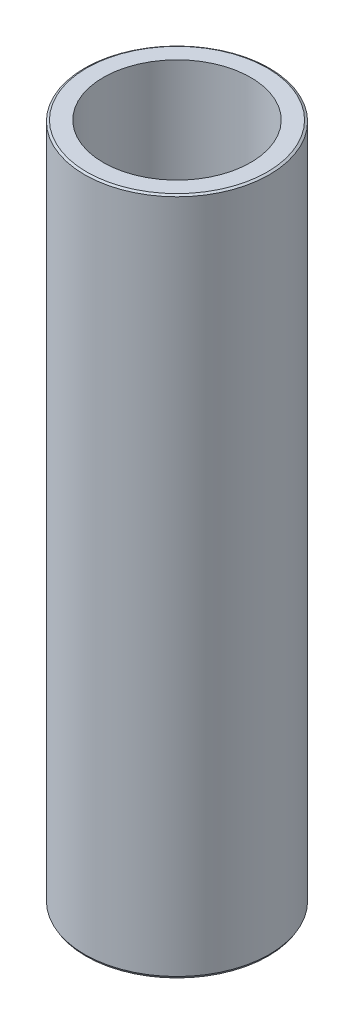
SolidWorks part; units mm, degrees
ref_plane "Front Plane" through (0, 0, 0) normal (0, 0, 1) x (1, 0, 0)
ref_plane "Top Plane" through (0, 0, 0) normal (0, 1, 0) x (1, 0, 0)
ref_plane "Right Plane" through (0, 0, 0) normal (1, 0, 0) x (0, 0, -1)
sketch "Sketch1" plane through (0, 0, 0) normal (0, 1, 0) x (1, 0, 0)
  circle A0 centre (0, 0) radius 50
  dimension "SHAFT_OD" = 100
extrude "Boss-Extrude1" add sketch "Sketch1" along normal blind 367.3901
sketch "Sketch2" plane through (0, 0, 0) normal (0, 1, 0) x (1, 0, 0)
  circle A0 centre (0, 0) radius 39.912
  dimension "BORE_D" = 79.8241
extrude "Cut-Extrude1" cut sketch "Sketch2" along normal through all
chamfer "Chamfer1" distance 0.6722 angle 60 2 edges at (0, 367.3901, 50) (0, 0, 50) first distance on face at (0, 367.3901, 50) first distance on face at (0, 0, 39.912)
